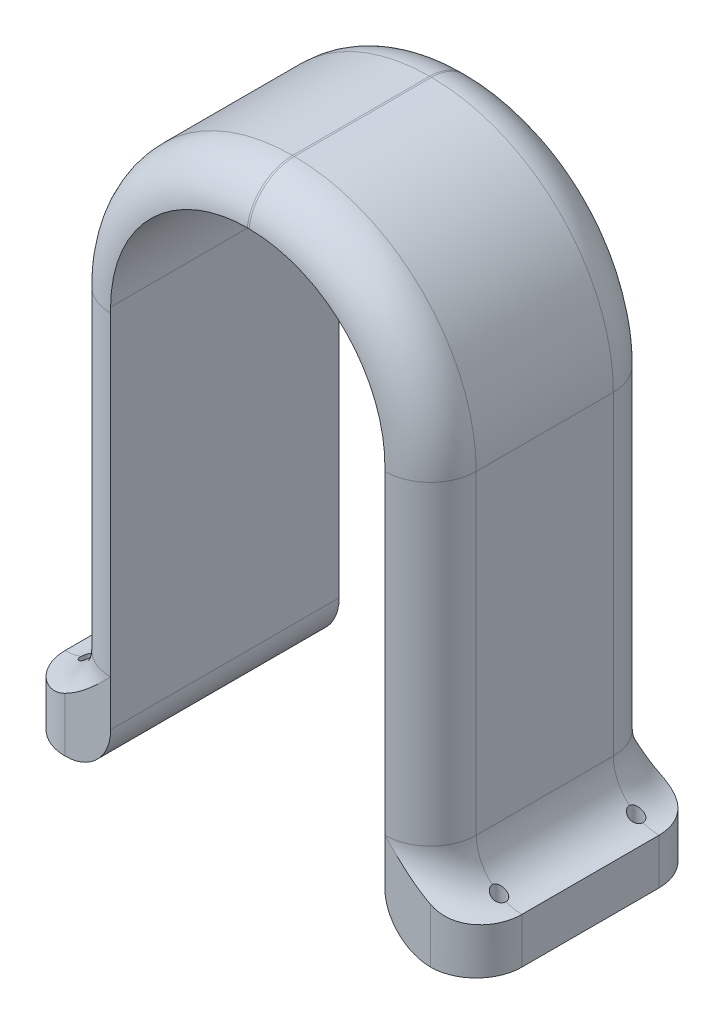
SolidWorks part; units mm, degrees
ref_plane "Front Plane" through (0, 0, 0) normal (0, 0, 1) x (1, 0, 0)
ref_plane "Top Plane" through (0, 0, 0) normal (0, 1, 0) x (1, 0, 0)
ref_plane "Right Plane" through (0, 0, 0) normal (1, 0, 0) x (0, 0, -1)
sketch "Sketch1" plane through (0, 0, 0) normal (0, 0, 1) x (1, 0, 0)
  line L0 (-7.4528, -1.2358) -> (-7.4528, -11.2358)
  line L1 (-7.4528, -1.2358) -> (2.5472, -1.2358)
  line L2 (-7.4528, -11.2358) -> (12.5472, -11.2358)
  line L3 (2.5472, -1.2358) -> (2.5472, 77.7041)
  line L4 (2.5472, -1.2358) -> (82.5472, -1.2358) construction
  line L5 (82.5472, -1.2358) -> (82.5472, 77.7041)
  line L6 (82.5472, -1.2358) -> (92.5472, -1.2358)
  line L7 (12.5472, -11.2358) -> (12.5472, 78.8642)
  line L8 (92.5472, -1.2358) -> (92.5472, -11.2358)
  line L9 (92.5472, -11.2358) -> (72.5472, -11.2358)
  line L10 (72.5472, -11.2358) -> (72.5472, 78.8642)
  line L11 (42.4472, 108.7642) -> (42.6472, 108.7642)
  line L12 (42.3472, 117.5041) -> (42.7472, 117.5041)
  arc A0 (42.4472, 108.7642) -> (12.5472, 78.8642) centre (42.4472, 78.8642) ccw
  arc A1 (72.5472, 78.8642) -> (42.6472, 108.7642) centre (42.6472, 78.8642) ccw
  arc A2 (42.3472, 117.5041) -> (2.5472, 77.7041) centre (42.3472, 77.7041) ccw
  arc A3 (82.5472, 77.7041) -> (42.7472, 117.5041) centre (42.7472, 77.7041) ccw
  point P14 (12.5472, 108.7642)
  point P17 (72.5472, 108.7642)
  point P20 (2.5472, 117.5041)
  point P21 (-99.5555, 55.2262)
  point P22 (-124.3785, 178.2259)
  dimension "D4" = 118.74
  dimension "D5" = 80
  dimension "D10" = 29.9
  dimension "D11" = 29.9
  dimension "D12" = 39.8
  dimension "D13" = 39.8
  dimension "D1" = 10
  dimension "D2" = 10
  dimension "D3" = 20
  dimension "D6" = 120
  dimension "10mm" = 10
  dimension "D7" = 10
  dimension "D8" = 20
  dimension "D9" = 120
extrude "Boss-Extrude2" add sketch "Sketch1" along normal blind 50
sketch "Sketch3" plane through (0, -1.2358, 0) normal (0, 1, 0) x (1, 0, 0)
  line L0 (-2.4528, -50) -> (-2.4528, -40) construction
  line L1 (2.5472, -50) -> (-7.4528, -50) construction
  line L2 (-2.4528, 0) -> (-2.4528, -10) construction
  line L3 (2.5472, 0) -> (-7.4528, 0) construction
  line L4 (87.5472, -50) -> (87.5472, -40) construction
  line L5 (92.5472, -50) -> (82.5472, -50) construction
  line L6 (87.5472, 0) -> (87.5472, -10) construction
  line L7 (92.5472, 0) -> (82.5472, 0) construction
  circle A0 centre (-2.4528, -40) radius 1.5
  circle A1 centre (-2.4528, -10) radius 1.5
  circle A2 centre (87.5472, -10) radius 1.5
  circle A3 centre (87.5472, -40) radius 1.5
  dimension "D2" = 3
  dimension "D4" = 3
  dimension "D7" = 3
  dimension "D8" = 3
  dimension "D1" = 10
  dimension "D3" = 10
  dimension "D5" = 10
  dimension "D6" = 10
extrude "Cut-Extrude1" cut sketch "Sketch3" against normal blind 50
fillet "Fillet2" radius 10 1 edges at (12.5472, -11.2358, 25)
fillet "Fillet3" radius 10 1 edges at (72.5472, -11.2358, 25)
fillet "Fillet8" radius 10 8 edges at (82.5472, 38.2341, 50) (2.5472, 38.2341, 50) (14.2043, 105.847, 50) (82.5472, 38.2341, 0) (2.5472, 38.2341, 0) (14.2043, 105.847, 0) (70.89, 105.847, 50) (70.89, 105.847, 0)
fillet "Fillet12" radius 10 3 edges at (79.6182, -1.2358, 2.9289) (82.5472, -1.2358, 25) (79.6182, -1.2358, 47.0711)
fillet "Fillet13" radius 10 3 edges at (5.4761, -1.2358, 2.9289) (2.5472, -1.2358, 25) (5.4761, -1.2358, 47.0711)
fillet "Fillet14" radius 10 1 edges at (-7.4528, -6.2358, 50)
fillet "Fillet15" radius 10 1 edges at (92.5472, -6.2358, 50)
fillet "Fillet16" radius 10 1 edges at (92.5472, -6.2358, 0)
fillet "Fillet19" radius 10 1 edges at (-7.4528, -6.2358, 0)
